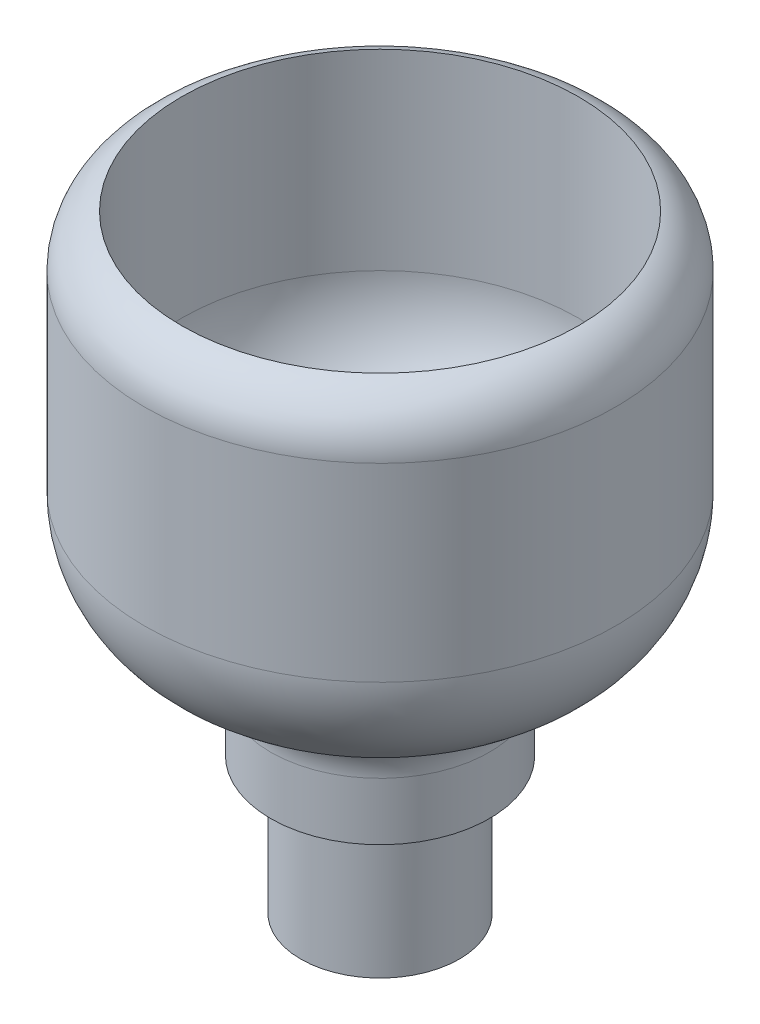
SolidWorks part; units mm, degrees
ref_plane "Front Plane" through (0, 0, 0) normal (0, 0, 1) x (1, 0, 0)
ref_plane "Top Plane" through (0, 0, 0) normal (0, 1, 0) x (1, 0, 0)
ref_plane "Right Plane" through (0, 0, 0) normal (1, 0, 0) x (0, 0, -1)
sketch "Sketch1" plane through (0, 0, 0) normal (0, 0, 1) x (1, 0, 0)
  line L0 (-122.2113, 0) -> (157.1675, 0) construction
  line L1 (0, 81.429) -> (0, -95.2489) construction
  line L2 (2.8, 5.7685) -> (2.8, 11.5369)
  line L3 (7.2548, 15.9917) -> (7.2548, 23.0026)
  line L4 (2.8, 5.7685) -> (4, 5.7685)
  line L5 (4, 5.7685) -> (4, 9.5612)
  line L6 (8.614, 14.1752) -> (8.614, 23.0026)
  line L7 (8.614, 23.0026) -> (7.2548, 23.0026)
  arc A0 (2.8, 11.5369) -> (7.2548, 15.9917) centre (2.8, 15.9917) ccw
  arc A1 (4, 9.5612) -> (8.614, 14.1752) centre (4, 14.1752) ccw
  dimension "D2" = 2.8
  dimension "D1" = 4
revolve "Revolve1" add sketch "Sketch1" angle 360 about L1
sketch "Sketch2" plane through (0, 5.7685, 0) normal (0, -1, 0) x (1, 0, 0)
  circle A0 centre (0, 0) radius 2.8 construction
  circle A1 centre (0, 0) radius 4 construction
  circle A2 centre (0, 0) radius 2.8
  circle A3 centre (0, 0) radius 4
fillet "Fillet2" radius 2 1 edges at (0, 23.0026, 8.614)
fillet "Fillet5" radius 2 1 edges at (0, 9.5612, 4)
sketch "Sketch4" plane through (0, 5.7685, 0) normal (0, -1, 0) x (1, 0, 0)
  circle A0 centre (0, 0) radius 2.8 construction
  circle A1 centre (0, 0) radius 2.8
  circle A2 centre (0, 0) radius 2.9
  dimension "D1" = 5.8
extrude "Boss-Extrude1" add sketch "Sketch4" along normal blind 5
